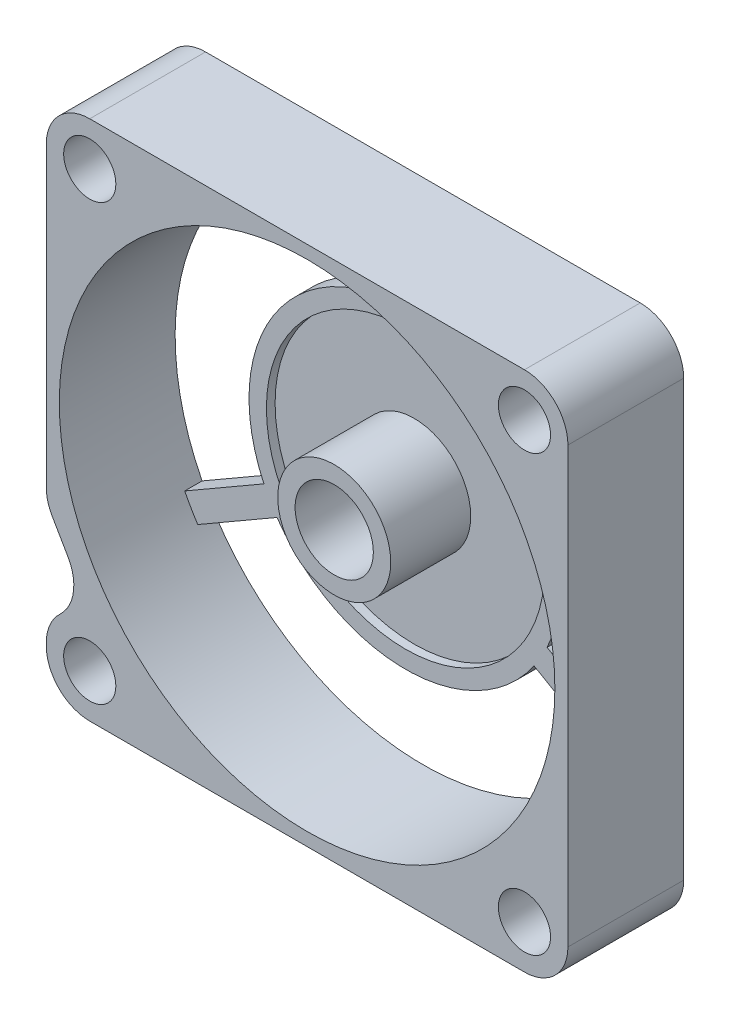
SolidWorks part; units mm, degrees
ref_plane "Front Plane" through (0, 0, 0) normal (0, 0, 1) x (1, 0, 0)
ref_plane "Top Plane" through (0, 0, 0) normal (0, 1, 0) x (1, 0, 0)
ref_plane "Right Plane" through (0, 0, 0) normal (1, 0, 0) x (0, 0, -1)
sketch "Sketch1" plane through (0, 0, 0) normal (0, 0, 1) x (1, 0, 0)
  line L1 (-15, 15) -> (15, 15)
  line L2 (-15, 15) -> (-15, -15)
  line L3 (-15, -15) -> (15, -15)
  line L4 (15, 15) -> (15, -15)
  line L5 (-15, 15) -> (15, -15) construction
  line L6 (-15, -15) -> (15, 15) construction
  line L7 (-12.5, 12.5) -> (12.5, 12.5) construction
  line L8 (-12.5, 12.5) -> (-12.5, -12.5) construction
  line L9 (-12.5, -12.5) -> (12.5, -12.5) construction
  line L10 (12.5, 12.5) -> (12.5, -12.5) construction
  line L11 (-12.5, 12.5) -> (12.5, -12.5) construction
  line L12 (-12.5, -12.5) -> (12.5, 12.5) construction
  circle A0 centre (0, 0) radius 14.25
  circle A1 centre (-12.5, 12.5) radius 1.5
  circle A2 centre (12.5, 12.5) radius 1.5
  circle A3 centre (12.5, -12.5) radius 1.5
  circle A4 centre (-12.5, -12.5) radius 1.5
  point P0 (0, 0)
  dimension "D2" = 28.5
  dimension "D3" = 25
  dimension "D4" = 3
  dimension "D1" = 30
extrude "Boss-Extrude1" add sketch "Sketch1" along normal blind 6.66
sketch "Sketch2" plane through (0, 0, 0) normal (0, 0, 1) x (1, 0, 0)
  line L0 (0, 0) -> (0, 14.25) construction
  line L4 (0, 0) -> (-12.3409, -7.125) construction
  line L6 (-0.75, 8.9687) -> (-0.75, 14.2302)
  line L8 (0, 14.25) -> (0, 0)
  line L10 (-12.6988, -6.4656) -> (-8.1421, -3.8348)
  line L12 (-12.3409, -7.125) -> (0, 0)
  arc A0 (-8.1421, -3.8348) -> (-0.75, 8.9687) centre (0, 0) cw
  circle A1 centre (0, 0) radius 14.25 construction
  arc A2 (-12.3409, -7.125) -> (-12.6988, -6.4656) centre (0, 0) cw
  circle A3 centre (0, 0) radius 14.25 construction
  arc A4 (-0.75, 14.2302) -> (0, 14.25) centre (0, 0) cw
  dimension "D1" = 120
  dimension "D2" = 9
  dimension "D3" = 0.75
  dimension "D4" = 0.75
extrude "Boss-Extrude2" add sketch "Sketch2" along normal blind 1
pattern_circular "CirPattern7" count 3 over 360 about axis through (0, 0, 6.66) along (0, 0, -1) of "Boss-Extrude2"
sketch "Sketch3" plane through (0, 0, 0) normal (0, 0, 1) x (1, 0, 0)
  circle A0 centre (0, 0) radius 2.25
  dimension "D1" = 4.5
extrude "Cut-Extrude2" cut sketch "Sketch3" along normal through all
sketch "Sketch4" plane through (0, 0, 1) normal (0, 0, 1) x (1, 0, 0)
  circle A0 centre (0, 0) radius 2.25 construction
  circle A1 centre (0, 0) radius 2.25
  circle A2 centre (0, 0) radius 3.25
  dimension "D1" = 1
extrude "Boss-Extrude3" add sketch "Sketch4" along normal blind 4.1
fillet "Fillet1" radius 2.5 4 edges at (15, -15, 3.33) (-15, -15, 3.33) (15, 15, 3.33) (-15, 15, 3.33)
sketch "Sketch5" plane through (0, 0, 6.66) normal (0, 0, 1) x (1, 0, 0)
  line L0 (15, 5.2831) -> (12.5, 9.6132) construction
  line L1 (15, -12.5) -> (15, 12.5) construction
  line L2 (12.5, 9.6132) -> (15, 11.0566) construction
  line L3 (15, 11.0566) -> (15, 5.2831) construction
  line L4 (12.5, 12.5) -> (13.75, 10.3349) construction
  line L5 (-15, -5.2831) -> (-12.5, -9.6132)
  line L6 (-15, -11.0566) -> (-15, -5.2831)
  line L7 (-12.5, -9.6132) -> (-15, -11.0566)
  line L8 (-12.5, -12.5) -> (-13.75, -10.3349) construction
  line L9 (-15, 12.5) -> (-15, -12.5) construction
  circle A0 centre (-12.5, -12.5) radius 1.5 construction
  circle A1 centre (-12.5, -12.5) radius 1.5 construction
  circle A2 centre (12.5, 12.5) radius 1.5 construction
  circle A3 centre (12.5, 12.5) radius 1.5 construction
  point P18 (0, 0)
  dimension "D2" = 2.5
  dimension "D1" = 30
  dimension "D3" = 2
sketch "Sketch6" plane through (0, 0, 1) normal (0, 0, 1) x (1, 0, 0)
  circle A0 centre (0, 0) radius 3.25
  circle A1 centre (0, 0) radius 8
  circle A2 centre (0, 0) radius 3.25 construction
  dimension "D1" = 8
extrude "Cut-Extrude4" cut sketch "Sketch6" against normal blind 0.5
extrude "Cut-Extrude5" cut sketch "Sketch5" against normal up to surface (5.66 mm away) up to face at (8, 0, 1)
fillet "Fillet4" radius 2.5 1 edges at (-12.5, -9.6132, 3.83)
fillet "Fillet5" radius 2.5 2 edges at (-15, -11.0566, 3.83) (-15, -5.2831, 3.83)
equation "\"D1@Boss-Extrude1\"=5.16+1.5"
